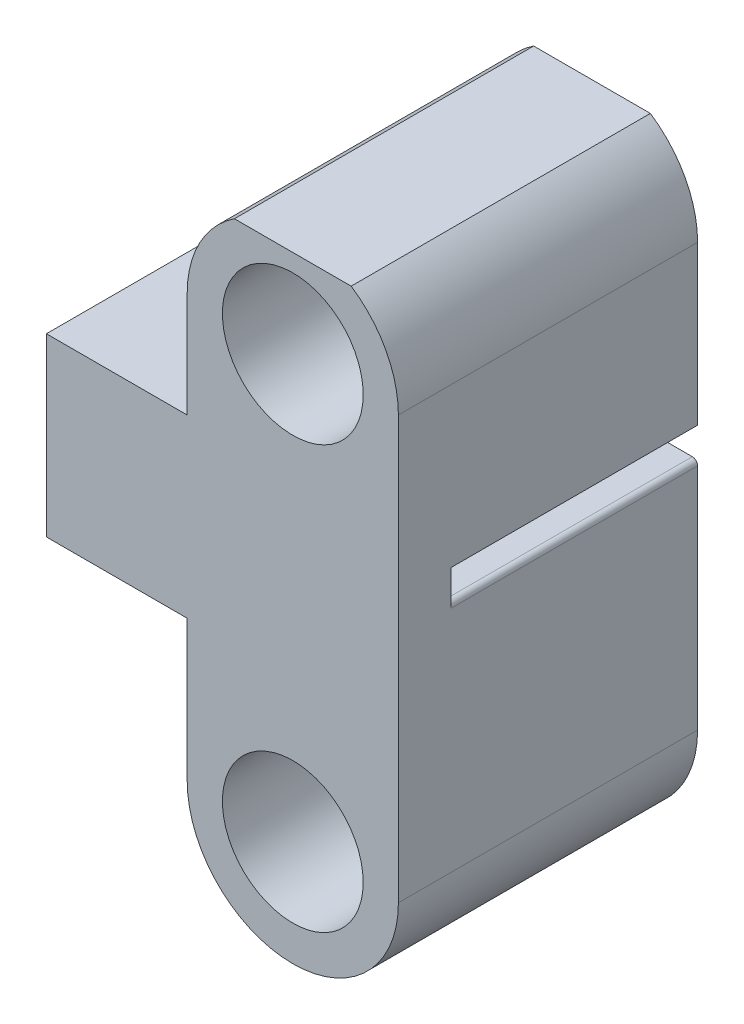
SolidWorks part; units mm, degrees
ref_plane "Front Plane" through (0, 0, 0) normal (0, 0, 1) x (1, 0, 0)
ref_plane "Top Plane" through (0, 0, 0) normal (0, 1, 0) x (1, 0, 0)
ref_plane "Right Plane" through (0, 0, 0) normal (1, 0, 0) x (0, 0, -1)
sketch "Sketch1" plane through (0, 0, 0) normal (0, 0, 1) x (1, 0, 0)
  line L0 (0, 0) -> (0, -12) construction
  line L1 (-3, 0) -> (-3, -12)
  line L2 (3, 0) -> (3, -12)
  arc A0 (3, 0) -> (-3, 0) centre (0, 0) ccw
  arc A1 (-3, -12) -> (3, -12) centre (0, -12) ccw
  circle A2 centre (0, 0) radius 2
  circle A3 centre (0, -12) radius 2
  dimension "D2" = 6
  dimension "D6" = 4
  dimension "D7" = 4
  dimension "D1" = 12
extrude "Boss-Extrude1" add sketch "Sketch1" along normal blind 8.5
sketch "Sketch2" plane through (3, 0, 0) normal (1, 0, 0) x (0, 0, -1)
  line L0 (-8.5, -6) -> (0, -6) construction
  line L1 (-8.5, -12) -> (-8.5, 0) construction
  line L2 (0, -12) -> (0, 0) construction
  line L3 (-4.25, 0) -> (-4.25, -12) construction
  line L4 (-8.5, 0) -> (0, 0) construction
  line L5 (-8.5, -12) -> (0, -12) construction
  circle A0 centre (-4.25, -8.5) radius 2
  dimension "D1" = 4
  dimension "D2" = 2.5
extrude "Cut-Extrude1" [suppressed] cut sketch "Sketch2" against normal through all
sketch "Sketch3" [suppressed] plane through (3, 0, 0) normal (1, 0, 0) x (0, 0, -1)
  line L1 (-0.6416, -8.5) -> (-2.4458, -5.375)
  line L2 (-2.4458, -5.375) -> (-6.0542, -5.375)
  line L3 (-6.0542, -5.375) -> (-7.8584, -8.5)
  line L4 (-7.8584, -8.5) -> (-6.0542, -11.625)
  line L5 (-6.0542, -11.625) -> (-2.4458, -11.625)
  line L6 (-2.4458, -11.625) -> (-0.6416, -8.5)
  line L7 (-1.8684, -4.375) -> (-6.6316, -4.375)
  line L8 (-6.6316, -4.375) -> (-9.0131, -8.5)
  line L9 (-9.0131, -8.5) -> (-6.6316, -12.625)
  line L10 (-6.6316, -12.625) -> (-1.8684, -12.625)
  line L11 (-1.8684, -12.625) -> (0.5131, -8.5)
  line L12 (0.5131, -8.5) -> (-1.8684, -4.375)
  circle A0 centre (-4.25, -8.5) radius 3.125 construction
  circle A1 centre (-4.25, -8.5) radius 4.125 construction
  dimension "D1" = 6.25
  dimension "D2" = 1
extrude "Boss-Extrude2" [suppressed] add sketch "Sketch3" along normal blind 2 and the other way blind 0.5
sketch "Sketch4" [suppressed] plane through (-3, 0, 0) normal (-1, 0, 0) x (0, 0, 1)
  line L0 (4.25, 0) -> (4.25, -6.5) construction
  line L1 (8.5, 0) -> (0, 0) construction
  line L3 (0.75, -2.75) -> (7.75, -2.75)
  line L4 (0.75, -2.75) -> (0.75, -5.75)
  line L5 (0.75, -5.75) -> (7.75, -5.75)
  line L6 (7.75, -2.75) -> (7.75, -5.75)
  line L7 (0.75, -2.75) -> (7.75, -5.75) construction
  line L8 (0.75, -5.75) -> (7.75, -2.75) construction
  circle A0 centre (4.25, -8.5) radius 2 construction
  point P7 (4.25, -4.25)
  dimension "D1" = 7
  dimension "D2" = 3
  dimension "D3" = 2.75
extrude "Cut-Extrude2" [suppressed] cut sketch "Sketch4" against normal through all
sketch "Sketch5" plane through (-3, 0, 0) normal (-1, 0, 0) x (0, 0, 1)
  line L0 (4.25, 0) -> (4.25, -12) construction
  line L1 (8.5, 0) -> (0, 0) construction
  line L2 (8.5, -12) -> (0, -12) construction
  line L3 (0, -6) -> (8.5, -6) construction
  line L4 (0, 0) -> (0, -12) construction
  line L5 (8.5, 0) -> (8.5, -12) construction
  line L7 (0, -15) -> (8.5, -15)
  line L8 (0, -15) -> (0, 3)
  line L9 (0, 3) -> (8.5, 3)
  line L10 (8.5, -15) -> (8.5, 3)
  line L11 (0, -15) -> (8.5, 3) construction
  line L12 (0, 3) -> (8.5, -15) construction
  point P12 (4.25, -6)
extrude "Cut-Extrude3" [suppressed] cut sketch "Sketch5" against normal through all flip side to cut
sketch "Sketch9" plane through (-3, 0, 0) normal (-1, 0, 0) x (0, 0, 1)
  line L0 (8.5, 0) -> (8.5, -12) construction
  line L1 (0, -3) -> (8.5, -3)
  line L2 (0, -3) -> (0, -8)
  line L3 (0, -8) -> (8.5, -8)
  line L4 (8.5, -3) -> (8.5, -8)
  line L5 (0, 0) -> (0, -12) construction
  line L6 (8.5, 0) -> (0, 0) construction
  dimension "D1" = 5
  dimension "D2" = 3
extrude "Boss-Extrude4" add sketch "Sketch9" along normal blind 4
sketch "Sketch6" plane through (3, 0, 0) normal (1, 0, 0) x (0, 0, -1)
  line L0 (0, -12) -> (0, 0) construction
  line L1 (0, -4.5) -> (-7, -4.5)
  line L2 (0, -4.5) -> (0, -6.1)
  line L3 (0, -6.1) -> (-7, -6.1)
  line L4 (-7, -4.5) -> (-7, -6.1)
  dimension "D1" = 1.6
  dimension "D2" = 4.5
  dimension "D3" = 7
extrude "Cut-Extrude5" cut sketch "Sketch6" against normal through all
sketch "Sketch7" plane through (0, 0, 7) normal (0, 0, -1) x (-1, 0, 0)
  line L0 (-3, -6.1) -> (-3, -5.5)
  line L1 (-3, -4.5) -> (-3, -6.1) construction
  line L2 (-2.85, -5.35) -> (-2.15, -5.35)
  line L3 (-2, -5.5) -> (-2, -6.1)
  line L4 (7, -6.1) -> (-3, -6.1) construction
  line L5 (-2, -6.1) -> (-3, -6.1)
  line L6 (-0.85, -5.35) -> (-0.15, -5.35)
  line L7 (0, -5.5) -> (0, -6.1)
  line L8 (0, -6.1) -> (-1, -6.1)
  line L9 (-1, -6.1) -> (-1, -5.5)
  line L10 (1.15, -5.35) -> (1.85, -5.35)
  line L11 (2, -5.5) -> (2, -6.1)
  line L12 (2, -6.1) -> (1, -6.1)
  line L13 (1, -6.1) -> (1, -5.5)
  line L14 (3.15, -5.35) -> (3.85, -5.35)
  line L15 (4, -5.5) -> (4, -6.1)
  line L16 (4, -6.1) -> (3, -6.1)
  line L17 (3, -6.1) -> (3, -5.5)
  line L18 (5.15, -5.35) -> (5.85, -5.35)
  line L19 (6, -5.5) -> (6, -6.1)
  line L20 (6, -6.1) -> (5, -6.1)
  line L21 (5, -6.1) -> (5, -5.5)
  arc A0 (-2.15, -5.35) -> (-2, -5.5) centre (-2.15, -5.5) cw
  arc A1 (-3, -5.5) -> (-2.85, -5.35) centre (-2.85, -5.5) cw
  arc A2 (-1, -5.5) -> (-0.85, -5.35) centre (-0.85, -5.5) cw
  arc A3 (-0.15, -5.35) -> (0, -5.5) centre (-0.15, -5.5) cw
  arc A4 (1, -5.5) -> (1.15, -5.35) centre (1.15, -5.5) cw
  arc A5 (1.85, -5.35) -> (2, -5.5) centre (1.85, -5.5) cw
  arc A6 (3, -5.5) -> (3.15, -5.35) centre (3.15, -5.5) cw
  arc A7 (3.85, -5.35) -> (4, -5.5) centre (3.85, -5.5) cw
  arc A8 (5, -5.5) -> (5.15, -5.35) centre (5.15, -5.5) cw
  arc A9 (5.85, -5.35) -> (6, -5.5) centre (5.85, -5.5) cw
  point P11 (-2, -5.35)
  point P14 (-3, -5.35)
  dimension "D3" = 0.15
  dimension "D1" = 1
  dimension "D2" = 0.75
  dimension "D4" = 5
extrude "Boss-Extrude3" add sketch "Sketch7" along normal through all
sketch "Sketch10" plane through (0, 0, 8.5) normal (0, 0, 1) x (1, 0, 0)
  line L1 (-2.5, 3.5) -> (2.5, 3.5)
  line L2 (-2.5, 3.5) -> (-2.5, 2.5)
  line L3 (-2.5, 2.5) -> (2.5, 2.5)
  line L4 (2.5, 3.5) -> (2.5, 2.5)
  line L5 (-2.5, 3.5) -> (2.5, 2.5) construction
  line L6 (-2.5, 2.5) -> (2.5, 3.5) construction
  arc A0 (3, 0) -> (-3, 0) centre (0, 0) ccw construction
  point P0 (0, 3)
  dimension "D1" = 1
  dimension "D2" = 5
extrude "Cut-Extrude6" cut sketch "Sketch10" against normal through all
equation "\"X-ROD-SPACING\"=45"
equation "\"Y-ROD-SPACING\"=75"
equation "\"Z-ROD-SPACING\"=17.5"
equation "\"Y-BED-OFFSET\"=2"
equation "\"Y-BED-ROD-INSET\"=3.5"
equation "\"Y-BED-SCREW-SPACING\"=209"
equation "\"Y-BED-SCREW-CUTOUT-SLOT-HEIGHT\"=2"
equation "\"T-SLOT-NUT-FILLET-RADIUS\"=0.5"
equation "\"T-SLOT-SCREW-SHAFT-RADIUS\"=1.55"
equation "\"T-SLOT-SCREW-SHAFT-CUTOUT-LENGTH\"=11"
equation "\"T-SLOT-NUT-DEPTH\"=3.5"
equation "\"T-SLOT-NUT-WIDTH\"=2.85"
equation "\"T-SLOT-NUT-END-DISTANCE\"=8"
equation "\"ACRYLIC-THICKNESS\"=10"
equation "\"ACRYLIC-THICKNESS2\"=4.5"
equation "\"ACRYLIC-TAB-CUTOUT-SIZE\"=\"ACRYLIC-THICKNESS\"+\"ACRYLIC-TAB-TOLERANCE\"*2"
equation "\"ACRYLIC-TAB-TOLERANCE\"=-.05"
equation "\"ACRYLIC-TAB-WIDTH\"=\"ACRYLIC-THICKNESS\""
equation "\"ACRYLIC-M3-HOLE\"=2.9"
equation "\"SMOOTHROD-CAP-SCREW-DISTANCE\"=20"
equation "\"FRAME-WIDTH-INNER\"=370"
equation "\"NEMA17-HOLE-SPACING\"=31"
equation "\"NEMA17-CENTRAL-CUTOUT\"=22.5"
equation "\"Z-BRACKET-REACH\"=55"
equation "\"Z-ROD-INSET\"=13.5"
equation "\"TOP-BRACKET-SPACING\"=40"
equation "\"SMOOTHROD-X-LENGTH\"=350"
equation "\"SMOOTHROD-Y-LENGTH\"=350"
equation "\"SMOOTHROD-Z-LENGTH\"=350"
equation "\"SMOOTHROD-TIGHTENING-HEADROOM\"=.25"
equation "\"LEADSCREW-Z-LENGTH\"=300"
equation "\"SCREW-LENGTH-FRAME\"=\"ACRYLIC-THICKNESS\" + 10"
equation "\"SCREW-LENGTH-MOTOR\"=\"ACRYLIC-THICKNESS\" + 5"
equation "\"SCREW-LENGTH-EXTRUDER\"=28"
equation "\"SCREW-HEAD-RADIUS\"=6"
equation "\"PRINTED-M3-HOLE\"=3.5"
equation "\"PRINTED-X-SMOOTHROD-DIAMETER\"=8.8"
equation "\"PRINTED-X-SMOOTHROD-CUTOUT\"=10"
equation "\"PRINTED-X-BASE-HEIGHT\"=10"
equation "\"PRINTED-LM8UU-CUTOUT-SIZE\"=15.5"
equation "\"PRINTED-LM8UU-CUTOUT-LENGTH\"=24.5"
equation "\"PRINTED-X-IDLER-HEIGHT\"=16"
equation "\"PRINTED-M3-NUT-AF\"=6.25"
equation "\"PSU-MOUNTING-WIDTH\"=95"
equation "\"PSU-MOUNTING-HEIGHT\"=177"
equation "\"Y-BELT-TO-ROD-DISTANCE\"=20"
equation "\"SPOOL-HOLDER-ROD-SPACING\"=150"
equation "\"ACRYLIC-X-CARRIAGE-WIDTH\"=55"
equation "\"ACRYLIC-X-CARRIAGE-HEIGHT\"=75"
equation "\"ACRYLIC-X-CARRIAGE-LM8UU-CUTOUT-WIDTH\"=24.25"
equation "\"ACRYLIC-X-CARRIAGE-LM8UU-CUTOUT-HEIGHT\"=11.0"
equation "\"ACRYLIC-X-CARRIAGE-SCREW-SPACING-X\"=15"
equation "\"ACRYLIC-X-CARRIAGE-SCREW-SPACING-Y\"=33"
equation "\"ACRYLIC-X-CARRIAGE-CENTER-TAB-SPACING\"=14"
equation "\"ACRYLIC-X-CARRIAGE-EXTRUDER-OFFSET\"=26"
equation "\"ACRYLIC-X-CARRIAGE-EXTRUDER-ANGLE\"=90"
equation "\"ACRYLIC-X-CARRIAGE-EXTRUDER-SHELF-DEPTH\"=\"ACRYLIC-X-CARRIAGE-EXTRUDER-OFFSET\" + 28"
equation "\"ACRYLIC-X-CARRIAGE-EXTRUDER-BRACE-SPACING\"=23"
equation "\"ACRYLIC-X-CARRIAGE-EXTRUDER-BRACE-TAB-OFFSET\"=20"
equation "\"ACRYLIC-X-CARRIAGE-EXTRUDER-BRACE-HEIGHT\"=35"
equation "\"ACRYLIC-X-CARRIAGE-EXTRUDER-BRACE-SCREW-SPACING\"=22"
equation "\"ACRYLIC-X-CARRIAGE-DUAL-WIDTH-MULTIPLIER\"=1.65"
equation "\"ACRYLIC-X-CARRIAGE-DUAL-HOTEND-SPACING\"=42"
equation "\"ACRYLIC-X-CARRIAGE-DUAL-WIDTH\"=75"
equation "\"ACRYLIC-X-CARRIAGE-DUAL-HOTEND-SEPARATION\"=36"
equation "\"ACRYLIC-X-CARRIAGE-DUAL-MOUNT-PLATE-DEPTH\"=75"
equation "\"ACRYLIC-X-CARRIAGE-DUAL-MOUNT-BRACE-WIDTH\"=33"
equation "\"ACRYLIC-X-CARRIAGE-DUAL-MOUNT-SCREW-WIDTH\"=40"
equation "\"BLOWER-FAN-WIDTH\"=15"
equation "\"D1@Sketch3\"=\"PRINTED-M3-NUT-AF\""
